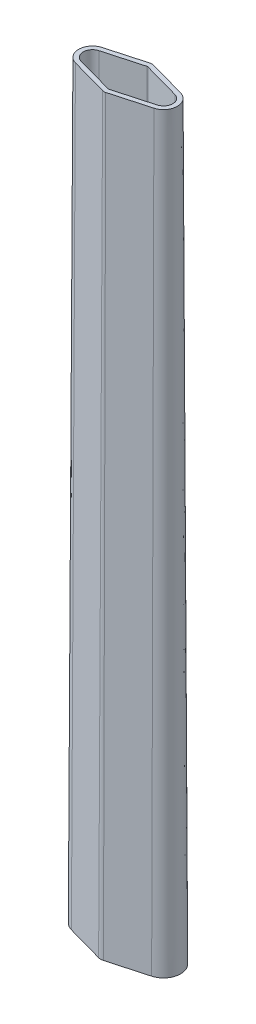
SolidWorks part; units mm, degrees
ref_plane "Front Plane" through (0, 0, 0) normal (0, 0, 1) x (1, 0, 0)
ref_plane "Top Plane" through (0, 0, 0) normal (0, 1, 0) x (1, 0, 0)
ref_plane "Right Plane" through (0, 0, 0) normal (1, 0, 0) x (0, 0, -1)
sketch "Sketch1" plane through (0, 0, 0) normal (0, 1, 0) x (1, 0, 0)
  line L0 (-13.378, 5.4914) -> (-0.8042, 8.9902)
  line L1 (0.8042, 8.9902) -> (13.378, 5.4914)
  line L2 (13.378, -5.4914) -> (0.8042, -8.9902)
  line L3 (-0.8042, -8.9902) -> (-13.378, -5.4914)
  line L4 (-33.1125, 0) -> (33.1125, 0) construction
  line L5 (0, 9.214) -> (0, -9.214) construction
  arc A0 (13.378, -5.4914) -> (13.378, 5.4914) centre (11.85, 0) ccw
  arc A1 (-13.378, -5.4914) -> (-13.378, 5.4914) centre (-11.85, 0) cw
  arc A2 (0.8042, -8.9902) -> (-0.8042, -8.9902) centre (0, -6.1) cw
  arc A3 (0.8042, 8.9902) -> (-0.8042, 8.9902) centre (0, 6.1) ccw
  point P17 (-17.55, 0)
  point P18 (17.55, 0)
  point P19 (0, 9.1)
  point P20 (0, -9.1)
  dimension "D3" = 5.7
  dimension "D4" = 3
  dimension "D1" = 10.9827
  dimension "D2" = 35.1
  dimension "D5" = 18.2
extrude "Boss-Extrude1" add sketch "Sketch1" along normal blind 250 draft 0.25
shell "Shell1" thickness 1.5 removed face at (0, 0, 0) removed face at (0, 250, 0)
